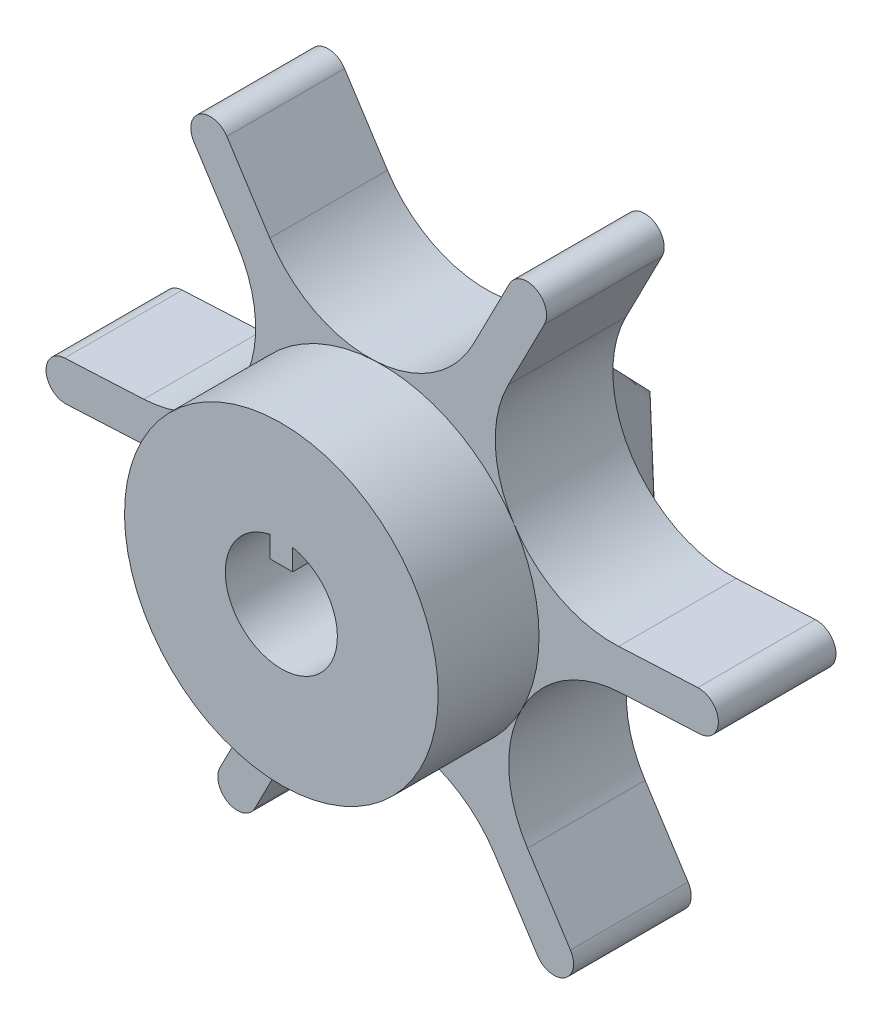
SolidWorks part; units mm, degrees
ref_plane "Front Plane" through (0, 0, 0) normal (0, 0, 1) x (1, 0, 0)
ref_plane "Top Plane" through (0, 0, 0) normal (0, 1, 0) x (1, 0, 0)
ref_plane "Right Plane" through (0, 0, 0) normal (1, 0, 0) x (0, 0, -1)
sketch "Sketch1" plane through (0, 0, 0) normal (0, 0, 1) x (1, 0, 0)
  line L0 (-33.6058, 45.6534) -> (-25.9397, 33.7658)
  line L1 (-30.6644, 47.5503) -> (-56.5119, -2.781) construction
  line L2 (-56.5119, -2.781) -> (-25.8475, -50.3313) construction
  line L3 (-25.8475, -50.3313) -> (30.6644, -47.5503) construction
  line L4 (30.6644, -47.5503) -> (56.5119, 2.781) construction
  line L5 (56.5119, 2.781) -> (25.8475, 50.3313) construction
  line L6 (25.8475, 50.3313) -> (-30.6644, 47.5503) construction
  line L7 (-27.723, 49.4471) -> (-20.0569, 37.5596)
  line L8 (22.7341, 51.9302) -> (16.2722, 39.3474)
  line L9 (28.961, 48.7324) -> (22.4991, 36.1496)
  line L10 (56.3399, 6.2768) -> (42.2119, 5.5815)
  line L11 (56.684, -0.7147) -> (42.556, -1.41)
  line L12 (33.6058, -45.6534) -> (25.9397, -33.7658)
  line L13 (27.723, -49.4471) -> (20.0569, -37.5596)
  line L14 (-22.7341, -51.9302) -> (-16.2722, -39.3474)
  line L15 (-28.961, -48.7324) -> (-22.4991, -36.1496)
  line L16 (-56.3399, -6.2768) -> (-42.2119, -5.5815)
  line L17 (-56.684, 0.7147) -> (-42.556, 1.41)
  circle A0 centre (41.1797, 26.5562) radius 21 construction
  circle A1 centre (43.5882, -22.3846) radius 21 construction
  circle A2 centre (2.4085, -48.9408) radius 21 construction
  circle A3 centre (-41.1797, -26.5562) radius 21 construction
  circle A4 centre (-43.5882, 22.3846) radius 21 construction
  circle A5 centre (-2.4085, 48.9408) radius 21 construction
  circle A6 centre (0, 0) radius 49 construction
  circle A7 centre (-30.6644, 47.5503) radius 3.5
  circle A8 centre (25.8475, 50.3313) radius 3.5
  circle A9 centre (56.5119, 2.781) radius 3.5
  circle A10 centre (30.6644, -47.5503) radius 3.5
  circle A11 centre (-25.8475, -50.3313) radius 3.5
  circle A12 centre (-56.5119, -2.781) radius 3.5
  arc A13 (-42.556, 1.41) -> (-25.9397, 33.7658) centre (-43.5882, 22.3846) ccw
  arc A14 (-20.0569, 37.5596) -> (16.2722, 39.3474) centre (-2.4085, 48.9408) ccw
  arc A15 (22.4991, 36.1496) -> (42.2119, 5.5815) centre (41.1797, 26.5562) ccw
  arc A16 (42.556, -1.41) -> (25.9397, -33.7658) centre (43.5882, -22.3846) ccw
  arc A17 (20.0569, -37.5596) -> (-16.2722, -39.3474) centre (2.4085, -48.9408) ccw
  arc A18 (-22.4991, -36.1496) -> (-42.2119, -5.5815) centre (-41.1797, -26.5562) ccw
  point P25 (0, 0)
  point P36 (0, 0)
  point P60 (0, 0)
  point P77 (0, 0)
  dimension "D2" = 42
  dimension "D4" = 7
  dimension "D1" = 6
  dimension "D3" = 6
  dimension "D5" = 6
  dimension "D6" = 6
extrude "Boss-Extrude1" add sketch "Sketch1" along normal blind 21 contours A18 L15 A11 L14 A17 L13 A10 L12 A16 L11 A9 L10 A15 L9 A8 L8 A14 L7 A7 L0 A13 L17 A12 L16 | A12 | A7 | A8 | A9 | A10 | A11 region at (0, 0, 0) region at (-30.6644, 47.5503, 0) region at (-56.5119, -2.781, 0) region at (25.8475, 50.3313, 0) region at (-25.8475, -50.3313, 0) region at (56.5119, 2.781, 0) region at (30.6644, -47.5503, 0)
ref_plane "Plane1" through (0, 0, 0) normal (0.0492, -0.9988, 0) x (-0.9988, -0.0492, 0)
sketch "Sketch3" plane through (0, 0, 0) normal (0.0492, -0.9988, 0) x (-0.9988, -0.0492, 0)
  line L0 (0, 0) -> (-28, 0)
  line L1 (-28, 0) -> (0, 26.8135)
  line L2 (0, 26.8135) -> (0, 0)
  dimension "D1" = 28
revolve "Revolve1" add sketch "Sketch3" angle 360 about L2
sketch "Sketch4" plane through (0, 0, 21) normal (0, 0, 1) x (1, 0, 0)
  circle A0 centre (0, 0) radius 28
extrude "Boss-Extrude2" add sketch "Sketch4" along normal blind 18
sketch "Sketch5" plane through (0, 0, 39) normal (0, 0, 1) x (1, 0, 0)
  circle A0 centre (0, 0) radius 10
  dimension "D1" = 20
extrude "Cut-Extrude1" cut sketch "Sketch5" against normal blind 30
sketch "Sketch6" plane through (0, 0, 9) normal (0, 0, 1) x (1, 0, 0)
  line L1 (2, 14) -> (-2, 14)
  line L2 (2, 14) -> (2, 6)
  line L3 (2, 6) -> (-2, 6)
  line L4 (-2, 14) -> (-2, 6)
  line L5 (2, 14) -> (-2, 6) construction
  line L6 (2, 6) -> (-2, 14) construction
  circle A0 centre (0, 0) radius 10 construction
  point P0 (0, 10)
  dimension "D1" = 4
  dimension "D2" = 8
extrude "Boss-Extrude3" add sketch "Sketch6" along normal up to surface (30 mm away) up to face at (10, 0, 39)
